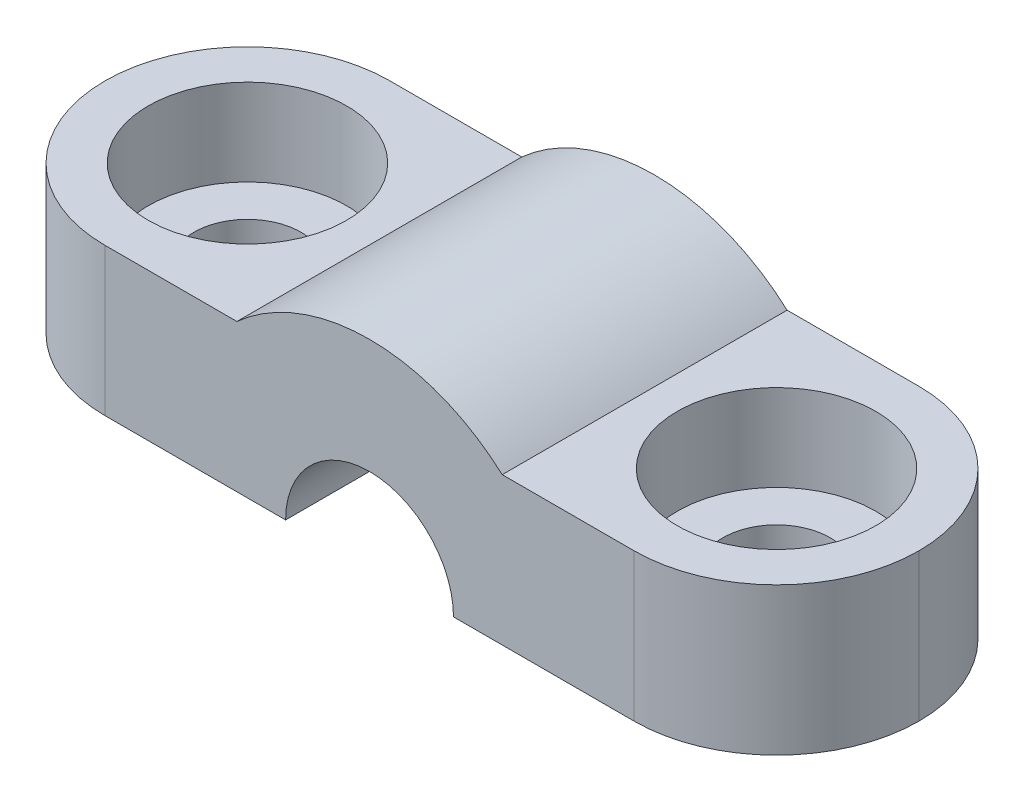
SolidWorks part; units mm, degrees
material "ABS"
ref_plane "Front Plane" through (0, 0, 0) normal (0, 0, 1) x (1, 0, 0)
ref_plane "Top Plane" through (0, 0, 0) normal (0, 1, 0) x (1, 0, 0)
ref_plane "Right Plane" through (0, 0, 0) normal (1, 0, 0) x (0, 0, -1)
ref_axis "Axis1" through (0, 0, 0) along (0, 0, 1)
sketch "Sketch1" plane through (0, 0, 0) normal (0, 1, 0) x (1, 0, 0)
  line L1 (-20, 7) -> (20, 7)
  line L2 (-20, 7) -> (-20, -7)
  line L3 (-20, -7) -> (20, -7)
  line L4 (20, 7) -> (20, -7)
  line L5 (-20, 7) -> (20, -7) construction
  line L6 (-20, -7) -> (20, 7) construction
  point P0 (0, 0)
  dimension "D1" = 14
  dimension "D2" = 40
extrude "Boss-Extrude1" add sketch "Sketch1" along normal blind 7.25
fillet "Fillet1" radius 7 4 edges at (-20, 3.625, 7) (20, 3.625, 7) (20, 3.625, -7) (-20, 3.625, -7)
sketch "Sketch2" plane through (0, 7.25, 0) normal (0, 1, 0) x (1, 0, 0)
  line L0 (0, 0) -> (0, 10.3236) construction
  circle A0 centre (-13, 0) radius 2.625
  circle A1 centre (13, 0) radius 2.625
  dimension "D1" = 5.25
extrude "Cut-Extrude1" cut sketch "Sketch2" against normal through all
sketch "Sketch3" plane through (0, 7.25, 0) normal (0, 1, 0) x (1, 0, 0)
  line L0 (0, 0) -> (0, 13.794) construction
  circle A0 centre (-13, 0) radius 4.875
  circle A1 centre (13, 0) radius 4.875
  dimension "D1" = 9.75
extrude "Cut-Extrude2" cut sketch "Sketch3" against normal blind 4.25
sketch "Sketch4" plane through (0, 0, 7) normal (0, 0, 1) x (1, 0, 0)
  line L0 (-13, 7.25) -> (13, 7.25) construction
  line L5 (13, 7.25) -> (-13, 7.25)
  line L6 (-13, 7.25) -> (-13, 0)
  line L7 (-13, 0) -> (13, 0)
  line L8 (13, 0) -> (13, 7.25)
  line L9 (6.5192, 7.25) -> (-6.5192, 7.25)
  arc A0 (6.5192, 7.25) -> (-6.5192, 7.25) centre (0, 0) ccw
  dimension "D1" = 9.75
  dimension "D2" = 0
extrude "Boss-Extrude2" add sketch "Sketch4" against normal up to surface (14 mm away) up to face at (0, 3.625, -7)
sketch "Sketch5" plane through (0, 0, 7) normal (0, 0, 1) x (1, 0, 0)
  line L0 (-13, 0) -> (13, 0) construction
  circle A0 centre (0, 0) radius 4.125
  dimension "D1" = 8.25
extrude "Cut-Extrude3" cut sketch "Sketch5" against normal through all
